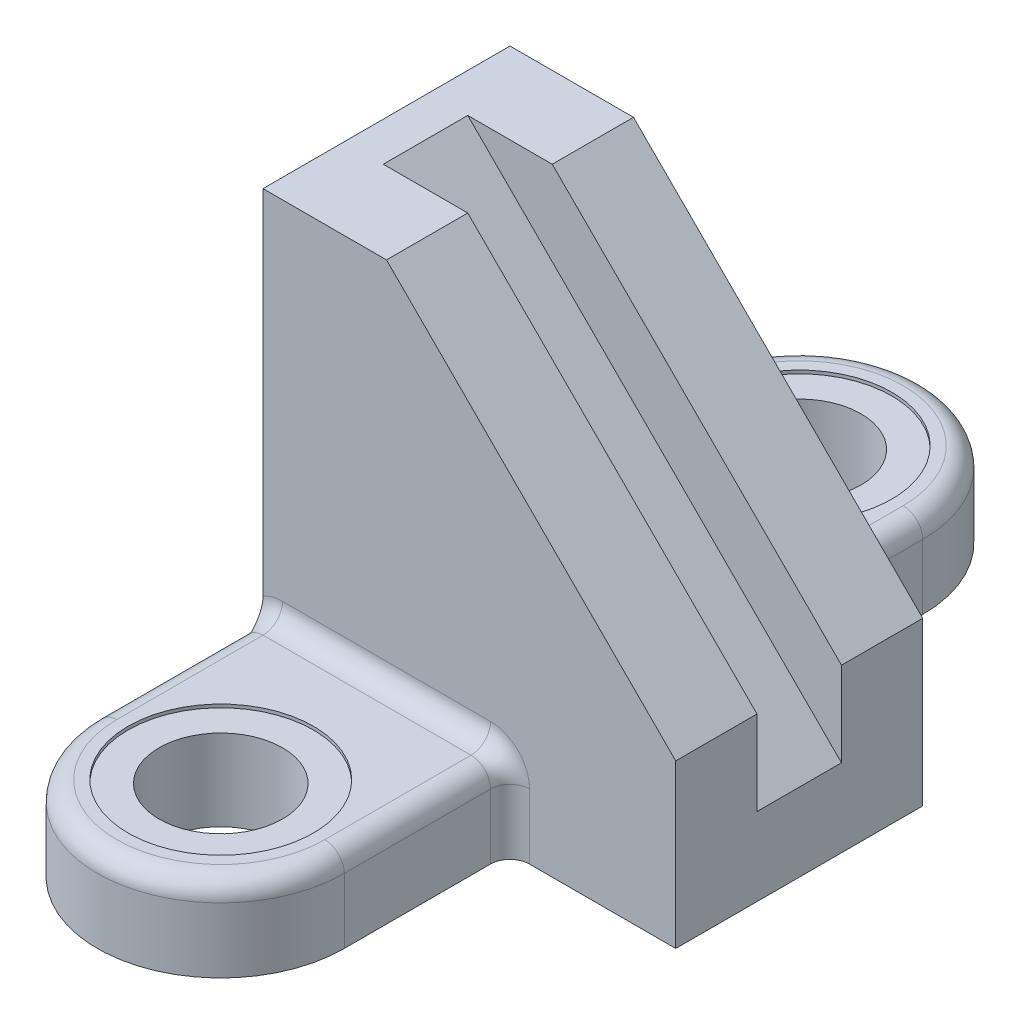
SolidWorks part; units mm, degrees
material "2014 Alloy"
ref_plane "Front Plane" through (0, 0, 0) normal (0, 0, 1) x (1, 0, 0)
ref_plane "Top Plane" through (0, 0, 0) normal (0, 1, 0) x (1, 0, 0)
ref_plane "Right Plane" through (0, 0, 0) normal (1, 0, 0) x (0, 0, -1)
sketch "Croquis1" plane through (0, 0, 0) normal (0, 0, 1) x (1, 0, 0)
  line L0 (0, 0) -> (0, 139)
  line L1 (38, 139) -> (127, 50)
  line L2 (127, 50) -> (127, 0)
  line L3 (127, 0) -> (0, 0)
  line L4 (38, 139) -> (0, 139)
  dimension "D1" = 38
  dimension "D2" = 127
  dimension "D3" = 50
  dimension "D4" = 45
extrude "Saliente-Extruir1" add sketch "Croquis1" along normal mid plane 76
sketch "Croquis2" plane through (0, 139, 0) normal (0, 1, 0) x (1, 0, 0)
  line L0 (38, 0) -> (38, 13)
  line L1 (38, -38) -> (38, 38) construction
  line L2 (38, 13) -> (12, 13)
  line L3 (12, 13) -> (12, -13)
  line L4 (12, -13) -> (38, -13)
  line L5 (38, -13) -> (38, 0)
  dimension "D1" = 26
  dimension "D2" = 26
  dimension "D3" = 13
extrude "Cortar-Extruir1" cut sketch "Croquis2" along direction (-0.7071, 0.7071, 0) on the side against the normal through all
sketch "Croquis3" plane through (0, 0, 0) normal (0, -1, 0) x (1, 0, 0)
  line L0 (0, 38) -> (0, 89)
  line L2 (76, 89) -> (76, 38)
  line L3 (0, 38) -> (127, 38) construction
  line L4 (76, 38) -> (0, 38)
  arc A0 (0, 89) -> (76, 89) centre (38, 89) cw
  circle A1 centre (38, 89) radius 19
  dimension "D3" = 38
  dimension "D2" = 76
extrude "Saliente-Extruir3" add sketch "Croquis3" against normal blind 26
fillet "Redondeo1" radius 6 3 edges at (0, 26, 63.5) (38, 26, 127) (76, 26, 63.5)
sketch "Croquis4" plane through (0, 26, 0) normal (0, 1, 0) x (1, 0, 0)
  circle A0 centre (38, -89) radius 28.5
  dimension "D1" = 57
extrude "Cortar-Extruir2" cut sketch "Croquis4" against normal blind 1
mirror "Simetría1" about plane through (0, 0, 0) normal (0, 0, 1) of "Redondeo1", "Saliente-Extruir3", "Cortar-Extruir2"
fillet "Redondeo2" radius 6 8 edges at (1.7574, 24.2426, -38) (76, 10, -38) (74.2426, 24.2426, -38) (1.7574, 24.2426, 38) (76, 10, 38) (74.2426, 24.2426, 38) (38, 26, -38) (38, 26, 38)
